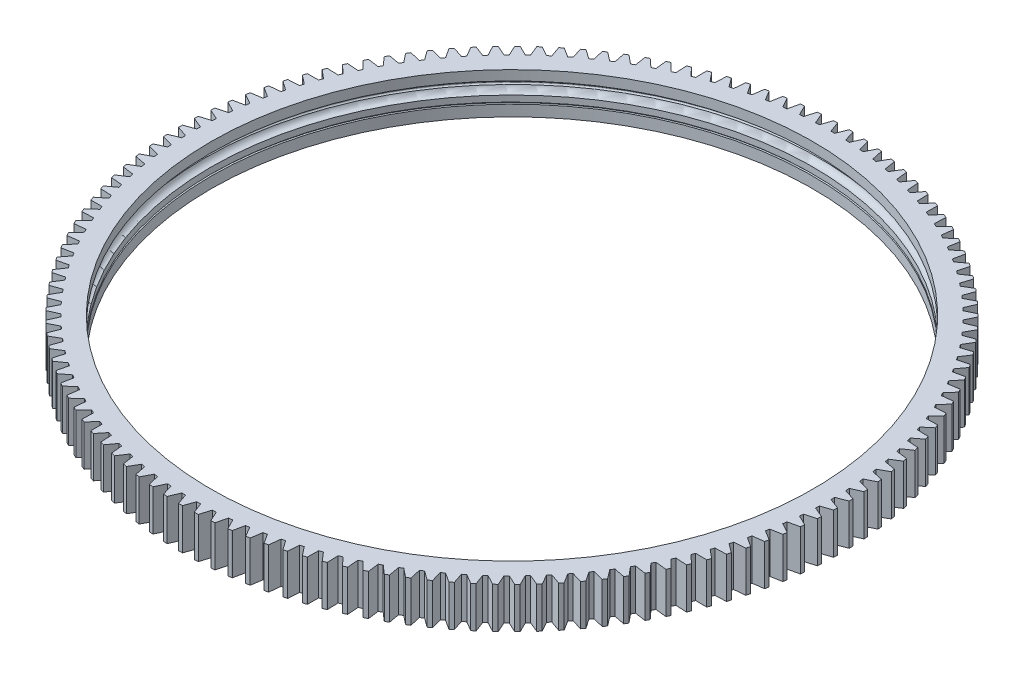
SolidWorks part; units mm, degrees
ref_plane "Plan de face" through (0, 0, 0) normal (0, 0, 1) x (1, 0, 0)
ref_plane "Plan de dessus" through (0, 0, 0) normal (0, 1, 0) x (1, 0, 0)
ref_plane "Plan de droite" through (0, 0, 0) normal (1, 0, 0) x (0, 0, -1)
sketch "Esquisse1" plane through (0, 0, 0) normal (0, 0, 1) x (1, 0, 0)
  line L0 (0, 0) -> (-539.2, 0) construction
  line L1 (-539.2, 0) -> (-539.2, 58) construction
  line L2 (-539.2, 58) -> (0, 58) construction
  line L3 (0, 58) -> (0, 0) construction
  line L4 (-539.2, 0) -> (-492.5, 0) construction
  line L5 (-492.5, 0) -> (-492.5, 10) construction
  line L6 (-492.5, 10) -> (-492.5, 30) construction
  line L7 (-492.5, 58) -> (-492.5, 42.7532) construction
  line L8 (-492.5, 58) -> (-539.2, 58) construction
  line L9 (-492.5, 20) -> (-502, 20) construction
  line L10 (-502, 20) -> (-504, 20) construction
  line L11 (-490.5, 58) -> (-490.5, 49) construction
  line L12 (-490.5, 49) -> (-487.5, 49) construction
  line L13 (-487.5, 49) -> (-487.5, 46) construction
  line L14 (-492.5, 58) -> (-492.5, 30) construction
  line L15 (-492.5, 42.7532) -> (-492.5, 58) construction
  line L16 (-491.5, 58) -> (-491.5, 0) construction
  line L17 (-490.5, 30) -> (-490.5, 58) construction
  line L18 (-490.5, 58) -> (-443, 58) construction
  line L19 (-443, 58) -> (-443, 0) construction
  line L20 (-443, 0) -> (-490.5, 0) construction
  line L21 (-487.5, 46) -> (-490.5, 46) construction
  line L22 (-490.5, 46) -> (-490.5, 30) construction
  line L23 (-490.5, 0) -> (-490.5, 10) construction
  line L24 (-490.5, 46) -> (-492.5, 46) construction
  line L25 (-492.5, 46) -> (-539.2, 46) construction
  line L26 (-539.2, 46) -> (-539.2, -21) construction
  line L27 (-492.5, 58) -> (-490.5, 58) construction
  line L28 (-539.2, -21) -> (-492.5, -21) construction
  line L29 (-492.5, 30) -> (-492.5, 46)
  line L30 (-492.5, 0) -> (-492.5, -3) construction
  line L31 (-492.5, -3) -> (-495.5, -3) construction
  line L32 (-495.5, -3) -> (-495.5, 0) construction
  line L33 (-495.5, 0) -> (-492.5, 0) construction
  line L34 (-492.5, 0) -> (-492.5, -21) construction
  line L35 (-492.5, 46) -> (-539.2, 46)
  line L36 (-539.2, 46) -> (-539.2, -21)
  line L37 (-539.2, -21) -> (-492.5, -21)
  line L38 (-492.5, -21) -> (-492.5, -3)
  line L39 (-492.5, -3) -> (-495.5, -3)
  line L40 (-495.5, -3) -> (-495.5, 0)
  line L41 (-495.5, 0) -> (-492.5, 0)
  line L42 (-492.5, 0) -> (-492.5, 10)
  arc A0 (-492.5, 30) -> (-492.5, 10) centre (-492.5, 20) ccw
  arc A1 (-502.3026, 21.977) -> (-502.3026, 18.023) centre (-502, 20) ccw
  arc A2 (-502.3026, 18.023) -> (-492.5, 10) centre (-492.5, 20) ccw construction
  arc A3 (-492.5, 30) -> (-502.3026, 21.977) centre (-492.5, 20) ccw construction
  arc A4 (-480.6974, 21.977) -> (-480.6974, 18.023) centre (-481, 20) cw construction
  arc A5 (-490.5, 30) -> (-490.5, 10) centre (-490.5, 20) cw construction
  arc A6 (-490.5, 30) -> (-480.6974, 21.977) centre (-490.5, 20) cw construction
  arc A7 (-480.6974, 18.023) -> (-490.5, 10) centre (-490.5, 20) cw construction
  dimension "D7" = 10
  dimension "D8" = 9.5
  dimension "D9" = 2
  dimension "D2" = 3
  dimension "D3" = 20
  dimension "D4" = 3
  dimension "D5" = 490.5
  dimension "D6" = 58
  dimension "D10" = 12
  dimension "D11" = 1
  dimension "D12" = 3
  dimension "D13" = 3
  dimension "D14" = 67
  dimension "D15" = 443
  dimension "D17" = 539.2
revolve "Révolution1" add sketch "Esquisse1" angle 360 about L3 region at (-516.9506, 12.1328, 0)
ref_axis "Axe2" through (0, 45.15, 0) along (0, -1, 0)
sketch "Esquisse2" plane through (0, -21, 0) normal (0, -1, 0) x (-1, 0, 0)
  line L0 (0, 0) -> (507.5, 0) construction
  circle A0 centre (507.5, 0) radius 8
  dimension "D2" = 16
  dimension "D1" = 507.5
extrude "Enlèv. mat.-Extru.4" cut sketch "Esquisse2" against normal blind 1
hole_wizard "Dégagement M161" positions "Esquisse4" profile "Esquisse3" hole size "M16" standard "ISO"
sketch "Esquisse4" plane through (0, -21, 0) normal (0, -1, 0) x (-1, 0, 0)
  point P0 (507.5, 0)
sketch "Esquisse3" plane through (-507.5, -21, 0) normal (1, 0, 0) x (0, 0, -1)
  line L0 (0, 0) -> (0, 23.2082)
  line L1 (0, 23.2082) -> (9.5, 17.5)
  line L2 (9.5, 17.5) -> (9.5, 0)
  line L5 (9.5, 0) -> (0, 0)
  line L10 (0, 23.2082) -> (-9.5, 17.5) construction
  line L11 (0, -6.35) -> (0, 107.95) construction
  dimension "Diamètre du perçage" = 19
  dimension "Profondeur du perçage" = 17.5
  dimension "Angle de pointe" = 118
pattern_circular "Répétition circulaire1" count 30 over 360 about axis through (0, 45.15, 0) along (0, -1, 0) of "Dégagement M161"
sketch "Esquisse5" plane through (0, 46, 0) normal (0, 1, 0) x (1, 0, 0)
  line L0 (0, 0) -> (0, -539.2) construction
  line L1 (0, 0) -> (25.407, -538.6011) construction
  line L2 (0, -539.2) -> (6.1649, -521.9636)
  line L3 (6.1649, -521.9636) -> (12.329, -521.8544)
  line L4 (12.329, -521.8544) -> (19.1007, -538.8616)
  line L5 (19.1007, -538.8616) -> (25.407, -538.6011)
  line L6 (19.1007, -538.8616) -> (0, 0) construction
  line L7 (0, 0) -> (12.329, -521.8544) construction
  line L8 (6.1649, -521.9636) -> (0, 0) construction
  line L9 (0, -539.2) -> (0, -556.8318)
  line L10 (0, -556.8318) -> (25.407, -556.2299)
  line L11 (25.407, -556.2299) -> (25.407, -538.6011)
  circle A0 centre (0, 0) radius 539.2 construction
  circle A1 centre (0, 0) radius 532 construction
  circle A2 centre (0, 0) radius 522 construction
  dimension "D1" = 1078.4
  dimension "D6" = 1064
  dimension "D7" = 1044
  dimension "D2" = 2.701
  dimension "D3" = 0.677
  dimension "D4" = 0.677
  dimension "D5" = 0.677
extrude "Enlèv. mat.-Extru.5" cut sketch "Esquisse5" against normal through all
pattern_circular "Répétition circulaire5" count 133 over 360 about axis through (0, 45.15, 0) along (0, -1, 0) of "Enlèv. mat.-Extru.5"
